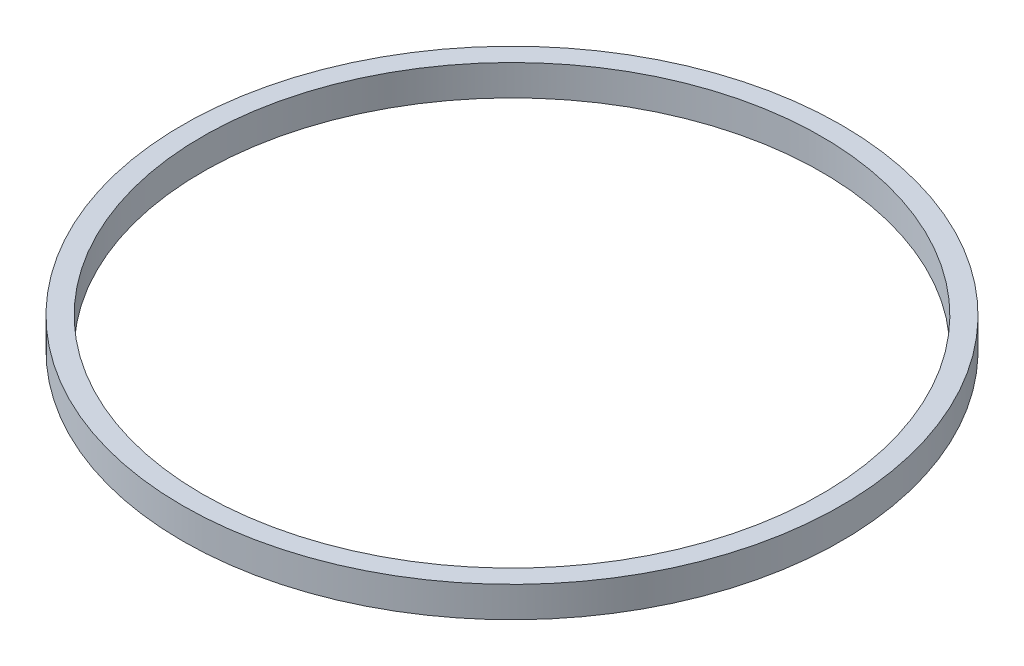
SolidWorks part; units mm, degrees
ref_plane "Front Plane" through (0, 0, 0) normal (0, 0, 1) x (1, 0, 0)
ref_plane "Top Plane" through (0, 0, 0) normal (0, 1, 0) x (1, 0, 0)
ref_plane "Right Plane" through (0, 0, 0) normal (1, 0, 0) x (0, 0, -1)
sketch "Sketch1" plane through (0, 0, 0) normal (0, 1, 0) x (1, 0, 0)
  circle A0 centre (0, 0) radius 20.2
  circle A1 centre (0, 0) radius 21.5
  dimension "D1" = 43
  dimension "D2" = 40.4
extrude "Boss-Extrude1" add sketch "Sketch1" along normal blind 2
